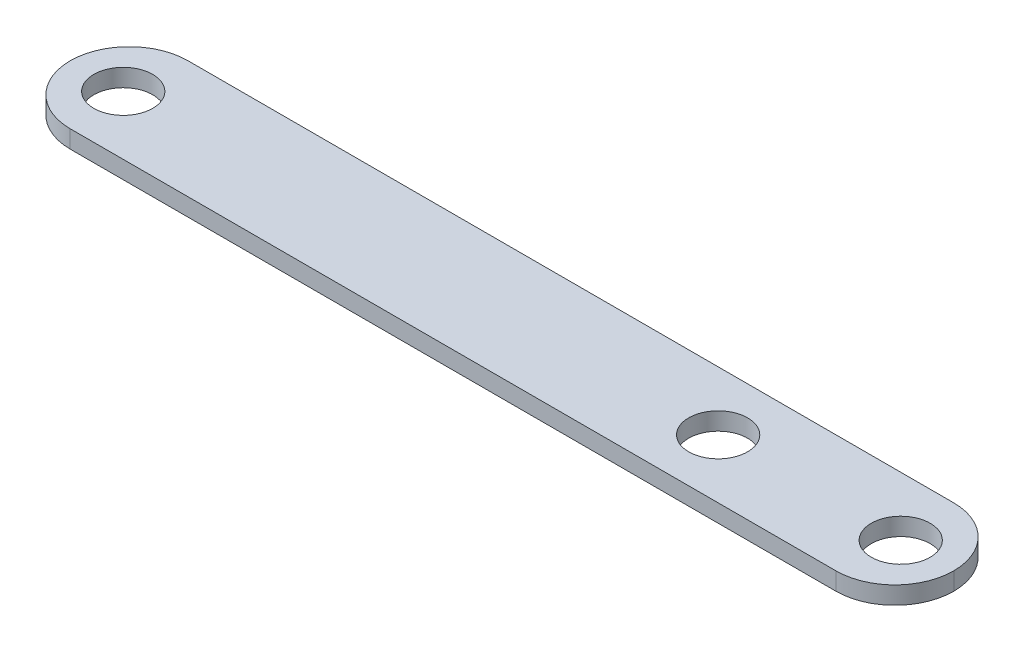
SolidWorks part; units mm, degrees
ref_plane "Front Plane" through (0, 0, 0) normal (0, 0, 1) x (1, 0, 0)
ref_plane "Top Plane" through (0, 0, 0) normal (0, 1, 0) x (1, 0, 0)
ref_plane "Right Plane" through (0, 0, 0) normal (1, 0, 0) x (0, 0, -1)
sketch "Sketch2" plane through (0, 0, 0) normal (0, 1, 0) x (1, 0, 0)
  line L1 (0, 0) -> (150, 0)
  line L2 (0, 0) -> (0, 20)
  line L3 (0, 20) -> (150, 20)
  line L4 (150, 0) -> (150, 20)
  dimension "D1" = 150
  dimension "D2" = 20
extrude "Boss-Extrude1" add sketch "Sketch2" along normal blind 3
sketch "Sketch3" plane through (0, 3, 0) normal (0, 1, 0) x (1, 0, 0)
  line L0 (150, 20) -> (0, 20) construction
  line L1 (0, 20) -> (0, 0) construction
  circle A0 centre (9, 10) radius 5
  dimension "D1" = 10
  dimension "D2" = 9
extrude "Cut-Extrude1" cut sketch "Sketch3" against normal through all
sketch "Sketch4" plane through (0, 3, 0) normal (0, 1, 0) x (1, 0, 0)
  line L0 (150, 20) -> (0, 20) construction
  line L1 (150, 0) -> (150, 20) construction
  circle A0 centre (141, 10) radius 5
  dimension "D1" = 10
  dimension "D2" = 9
extrude "Cut-Extrude2" cut sketch "Sketch4" against normal through all
fillet "Fillet1" radius 10 2 edges at (0, 1.5, -20) (0, 1.5, 0)
fillet "Fillet2" radius 10 2 edges at (150, 1.5, -20) (150, 1.5, 0)
sketch "Sketch5" plane through (0, 3, 0) normal (0, 1, 0) x (1, 0, 0)
  line L0 (10, 0) -> (140, 0) construction
  circle A0 centre (110, 10) radius 5
  point P6 (75, 0)
  dimension "D1" = 110
  dimension "D2" = 10
extrude "Cut-Extrude3" cut sketch "Sketch5" against normal through all
